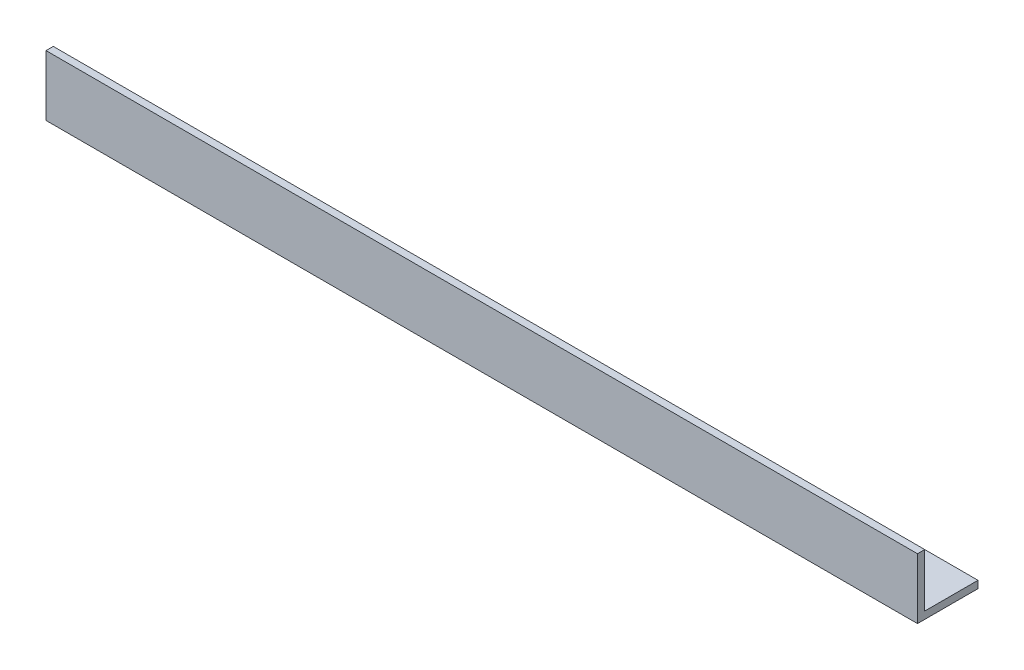
SolidWorks part; units mm, degrees
ref_plane "Спереди" through (0, 0, 0) normal (0, 0, 1) x (1, 0, 0)
ref_plane "Сверху" through (0, 0, 0) normal (0, 1, 0) x (1, 0, 0)
ref_plane "Справа" through (0, 0, 0) normal (1, 0, 0) x (0, 0, -1)
sketch "Эскиз1" plane through (0, 0, 0) normal (1, 0, 0) x (0, 0, -1)
  line L0 (0, 25) -> (0, 0)
  line L1 (0, 0) -> (25, 0)
extrude "Вытянуть-Тонкостенный1" add sketch "Эскиз1" along normal blind 360 thin thin type one direction reverse wall 3
ref_point "Точка2"
